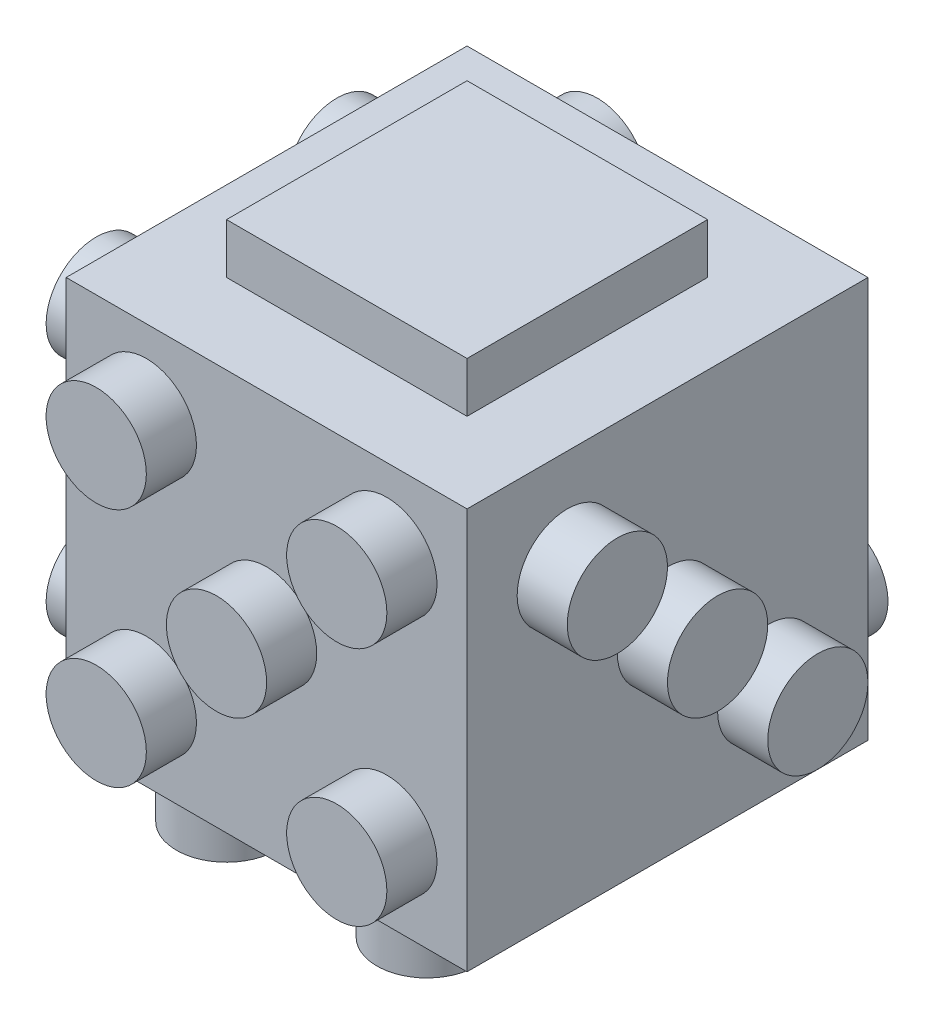
SolidWorks part; units mm, degrees
ref_plane "Front Plane" through (0, 0, 0) normal (0, 0, 1) x (1, 0, 0)
ref_plane "Top Plane" through (0, 0, 0) normal (0, 1, 0) x (1, 0, 0)
ref_plane "Right Plane" through (0, 0, 0) normal (1, 0, 0) x (0, 0, -1)
sketch "Sketch1" plane through (0, 0, 0) normal (0, 1, 0) x (1, 0, 0)
  line L1 (-12.5, 12.5) -> (12.5, 12.5)
  line L2 (-12.5, 12.5) -> (-12.5, -12.5)
  line L3 (-12.5, -12.5) -> (12.5, -12.5)
  line L4 (12.5, 12.5) -> (12.5, -12.5)
  line L5 (0, -12.5) -> (0, 12.5) construction
  line L6 (-12.5, 0) -> (12.5, 0) construction
  point P0 (0, 0)
  dimension "D1" = 25
  dimension "D2" = 25
extrude "Boss-Extrude1" add sketch "Sketch1" along normal blind 25
sketch "Sketch2" plane through (0, 25, 0) normal (0, 1, 0) x (1, 0, 0)
  line L1 (-6, 6) -> (6, 6)
  line L2 (-6, 6) -> (-6, -6)
  line L3 (-6, -6) -> (6, -6)
  line L4 (6, 6) -> (6, -6)
  line L5 (0, -6) -> (0, 6) construction
  line L6 (-6, 0) -> (6, 0) construction
  point P0 (0, 0)
  dimension "D1" = 12
  dimension "D2" = 12
sketch "Sketch3" plane through (0, 0, 0) normal (0, -1, 0) x (1, 0, 0)
  line L1 (10, 10) -> (-10, 10) construction
  line L2 (10, 10) -> (10, -10) construction
  line L3 (10, -10) -> (-10, -10) construction
  line L4 (-10, 10) -> (-10, -10) construction
  line L5 (0, -10) -> (0, 10) construction
  line L6 (10, 0) -> (-10, 0) construction
  line L7 (5, -7) -> (-5, -7) construction
  line L8 (5, -7) -> (5, 7) construction
  line L9 (5, 7) -> (-5, 7) construction
  line L10 (-5, -7) -> (-5, 7) construction
  line L11 (0, 7) -> (0, -7) construction
  line L12 (5, 0) -> (-5, 0) construction
  circle A0 centre (-5, 7) radius 2.5
  circle A1 centre (-5, 0) radius 2.5
  circle A2 centre (-5, -7) radius 2.5
  circle A3 centre (5, 7) radius 2.5
  circle A4 centre (5, 0) radius 2.5
  circle A5 centre (5, -7) radius 2.5
  point P0 (0, 0)
  point P4 (0, 0)
  dimension "D5" = 5
  dimension "D6" = 5
  dimension "D7" = 5
  dimension "D8" = 5
  dimension "D1" = 20
  dimension "D2" = 20
  dimension "D3" = 10
  dimension "D4" = 14
sketch "Sketch4" plane through (12.5, 0, 0) normal (1, 0, 0) x (0, 0, -1)
  line L4 (-12.5, 0) -> (12.5, 0)
  line L5 (12.5, 0) -> (12.5, 25)
  line L6 (12.5, 25) -> (-12.5, 25)
  line L7 (-12.5, 25) -> (-12.5, 0)
  line L8 (-12.5, 0) -> (12.5, 0)
  line L10 (12.5, 25) -> (-12.5, 25)
  line L11 (-12.5, 25) -> (-12.5, 0)
  circle A0 centre (-5, 17.5) radius 2.5
  circle A1 centre (0, 12.5) radius 2.5
  circle A2 centre (5, 7.5) radius 2.5
  dimension "D5" = 5
  dimension "D6" = 5
  dimension "D7" = 5
  dimension "D1" = 0
sketch "Sketch5" plane through (-12.5, 0, 0) normal (-1, 0, 0) x (0, 0, 1)
  line L0 (-12.5, 12.5) -> (0, 12.5) construction
  line L2 (-10, 22.5) -> (10, 22.5) construction
  line L3 (-10, 22.5) -> (-10, 2.5) construction
  line L4 (-12.5, 0) -> (12.5, 0)
  line L5 (12.5, 0) -> (12.5, 25)
  line L6 (12.5, 25) -> (-12.5, 25)
  line L7 (-12.5, 25) -> (-12.5, 0)
  line L8 (-12.5, 0) -> (12.5, 0)
  line L9 (12.5, 0) -> (12.5, 25)
  line L10 (12.5, 25) -> (-12.5, 25)
  line L11 (-12.5, 25) -> (-12.5, 0)
  line L12 (-10, 2.5) -> (10, 2.5) construction
  line L13 (10, 22.5) -> (10, 2.5) construction
  line L14 (0, 2.5) -> (0, 22.5) construction
  line L15 (-10, 12.5) -> (10, 12.5) construction
  line L16 (-6, 18.5) -> (6, 18.5) construction
  line L17 (-6, 18.5) -> (-6, 6.5) construction
  line L18 (-6, 6.5) -> (6, 6.5) construction
  line L19 (6, 18.5) -> (6, 6.5) construction
  line L20 (0, 6.5) -> (0, 18.5) construction
  line L21 (-6, 12.5) -> (6, 12.5) construction
  circle A0 centre (-6, 18.5) radius 2.5
  circle A1 centre (6, 18.5) radius 2.5
  circle A2 centre (6, 6.5) radius 2.5
  circle A3 centre (-6, 6.5) radius 2.5
  dimension "D6" = 5
  dimension "D7" = 5
  dimension "D8" = 5
  dimension "D9" = 5
  dimension "D2" = 20
  dimension "D3" = 20
  dimension "D4" = 12
  dimension "D5" = 12
  dimension "D1" = 0
sketch "Sketch7" plane through (0, 0, 12.5) normal (0, 0, 1) x (1, 0, 0)
  line L0 (0, 25) -> (0, 12.5) construction
  line L2 (-10, 22.5) -> (10, 22.5) construction
  line L3 (-10, 22.5) -> (-10, 2.5) construction
  line L4 (-12.5, 0) -> (12.5, 0)
  line L5 (12.5, 0) -> (12.5, 25)
  line L6 (12.5, 25) -> (-12.5, 25)
  line L7 (-12.5, 25) -> (-12.5, 0)
  line L8 (-12.5, 0) -> (12.5, 0)
  line L9 (12.5, 0) -> (12.5, 25)
  line L10 (12.5, 25) -> (-12.5, 25)
  line L11 (-12.5, 25) -> (-12.5, 0)
  line L12 (-10, 2.5) -> (10, 2.5) construction
  line L13 (10, 22.5) -> (10, 2.5) construction
  line L14 (0, 2.5) -> (0, 22.5) construction
  line L15 (-10, 12.5) -> (10, 12.5) construction
  line L16 (-6, 18.5) -> (6, 18.5) construction
  line L17 (-6, 18.5) -> (-6, 6.5) construction
  line L18 (-6, 6.5) -> (6, 6.5) construction
  line L19 (6, 18.5) -> (6, 6.5) construction
  line L20 (0, 6.5) -> (0, 18.5) construction
  line L21 (-6, 12.5) -> (6, 12.5) construction
  circle A0 centre (-6, 18.5) radius 2.5
  circle A1 centre (0, 12.5) radius 2.5
  circle A2 centre (6, 18.5) radius 2.5
  circle A3 centre (6, 6.5) radius 2.5
  circle A4 centre (-6, 6.5) radius 2.5
  dimension "D7" = 5
  dimension "D8" = 5
  dimension "D9" = 5
  dimension "D10" = 5
  dimension "D11" = 5
  dimension "D2" = 12.5
  dimension "D3" = 20
  dimension "D4" = 20
  dimension "D5" = 12
  dimension "D6" = 12
  dimension "D1" = 0
sketch "Sketch8" plane through (0, 0, -12.5) normal (0, 0, -1) x (-1, 0, 0)
  line L0 (0, 0) -> (0, 12.5) construction
  line L1 (10, 22.5) -> (-10, 2.5) construction
  line L2 (-10, 22.5) -> (10, 22.5) construction
  line L3 (-10, 22.5) -> (-10, 2.5) construction
  line L4 (-12.5, 0) -> (12.5, 0)
  line L5 (12.5, 0) -> (12.5, 25)
  line L6 (12.5, 25) -> (-12.5, 25)
  line L7 (-12.5, 25) -> (-12.5, 0)
  line L8 (-12.5, 0) -> (12.5, 0)
  line L9 (12.5, 0) -> (12.5, 25)
  line L10 (12.5, 25) -> (-12.5, 25)
  line L11 (-12.5, 25) -> (-12.5, 0)
  line L12 (-10, 2.5) -> (10, 2.5) construction
  line L13 (10, 22.5) -> (10, 2.5) construction
  line L14 (0, 2.5) -> (0, 22.5) construction
  line L15 (-10, 12.5) -> (10, 12.5) construction
  line L17 (-6, 18.5) -> (6, 18.5) construction
  line L18 (-6, 18.5) -> (-6, 6.5) construction
  line L19 (-6, 6.5) -> (6, 6.5) construction
  line L20 (6, 18.5) -> (6, 6.5) construction
  line L21 (0, 6.5) -> (0, 18.5) construction
  line L22 (-6, 12.5) -> (6, 12.5) construction
  circle A0 centre (6, 18.5) radius 2.5
  circle A1 centre (-6, 6.5) radius 2.5
  dimension "D7" = 5
  dimension "D8" = 5
  dimension "D2" = 12.5
  dimension "D3" = 20
  dimension "D4" = 20
  dimension "D5" = 12
  dimension "D6" = 12
  dimension "D1" = 0
scale "Scale1" bodies to scale 111 scale about centroid uniform scaling yes scale factor 0.8
extrude "Boss-Extrude2" add sketch "Sketch3" against normal up to surface (2.5 mm away) separate body contours A2 | A1 | A0 | A5 | A4 | A3 up to face at (0, 2.5, 0)
extrude "Boss-Extrude3" add sketch "Sketch7" against normal up to surface (2.5 mm away) contours A0 | A2 | A1 | A4 | A3 up to face at (0, 12.5, 10)
extrude "Boss-Extrude4" add sketch "Sketch5" against normal up to surface (2.5 mm away) contours A3 | A2 | A1 | A0 up to face at (-10, 12.5, 0)
extrude "Boss-Extrude5" add sketch "Sketch4" against normal up to surface (2.5 mm away) contours A2 | A1 | A0 up to face at (10, 12.5, 0)
extrude "Boss-Extrude6" add sketch "Sketch8" against normal up to surface (2.5 mm away) contours A1 | A0 up to face at (0, 12.5, -10)
extrude "Boss-Extrude7" add sketch "Sketch2" against normal up to surface (2.5 mm away) contours L4 L3 L2 L1 up to face at (0, 22.5, 0)
